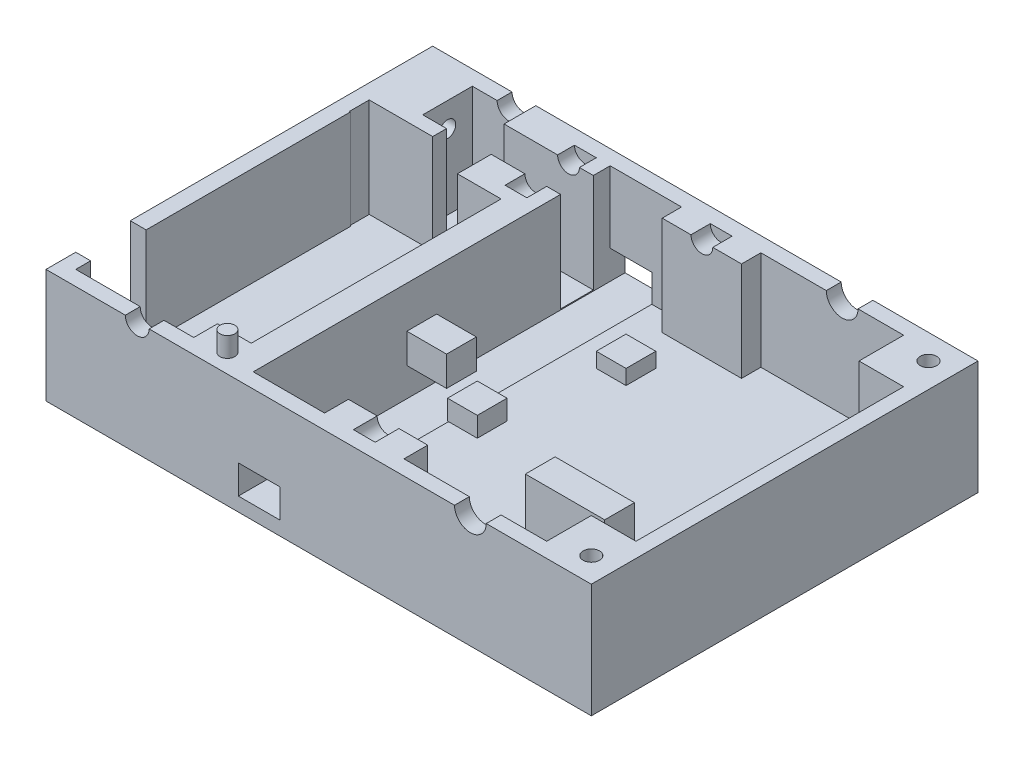
SolidWorks part; units mm, degrees
ref_plane "前视基准面" through (0, 0, 0) normal (0, 0, 1) x (1, 0, 0)
ref_plane "上视基准面" through (0, 0, 0) normal (0, 1, 0) x (1, 0, 0)
ref_plane "右视基准面" through (0, 0, 0) normal (1, 0, 0) x (0, 0, -1)
other "Configuration Table"
sketch "草图1" plane through (0, 0, 0) normal (0, 1, 0) x (1, 0, 0)
  line L1 (-27.5, 19.5) -> (27.5, 19.5)
  line L2 (-27.5, 19.5) -> (-27.5, -19.5)
  line L3 (-27.5, -19.5) -> (27.5, -19.5)
  line L4 (27.5, 19.5) -> (27.5, -19.5)
  line L5 (-27.5, 19.5) -> (27.5, -19.5) construction
  line L6 (-27.5, -19.5) -> (27.5, 19.5) construction
  point P0 (0, 0)
  dimension "D1" = 55
  dimension "D2" = 39
extrude "凸台-拉伸1" add sketch "草图1" along normal blind 11.5
shell "抽壳1" thickness 1.5 removed face at (0, 11.5, 0)
sketch "草图2" plane through (0, 0, -19.5) normal (0, 0, -1) x (-1, 0, 0)
  line L0 (7.9, 1.6) -> (4.1, 1.6) construction
  line L1 (3.9, 4.3) -> (8.1, 4.3)
  line L2 (3.9, 4.3) -> (3.9, 1.4)
  line L3 (3.9, 1.4) -> (8.1, 1.4)
  line L4 (8.1, 4.3) -> (8.1, 1.4)
  line L5 (7.9, 1.6) -> (7.9, 4.1) construction
  line L6 (7.9, 4.1) -> (4.1, 4.1) construction
  line L7 (4.1, 1.6) -> (4.1, 4.1) construction
  circle A0 centre (-15.3, 11.5) radius 1.6
  circle A1 centre (18.3, 11.5) radius 1.2
  circle A2 centre (-15.3, 11.5) radius 1.5 construction
  circle A3 centre (18.3, 11.5) radius 1 construction
  dimension "D1" = 0.1
  dimension "D2" = 0.2
  dimension "D3" = 0.2
  dimension "D4" = 0.2
  dimension "D5" = 0.2
  dimension "D6" = 0.2
extrude "切除-拉伸1" cut sketch "草图2" against normal through all
sketch "草图3" plane through (0, 1.5, 0) normal (0, 1, 0) x (1, 0, 0)
  line L0 (-25.8, -15.5) -> (-10.8, -15.5) construction
  line L5 (-10.7, 9.6) -> (-10.7, -15.6)
  line L6 (-15.1, 13) -> (-8.1, 13)
  line L7 (-15.1, 13) -> (-15.1, 9.6)
  line L8 (-15.1, 9.6) -> (-10.7, 9.6)
  line L10 (-17.1, -18) -> (13.7, -18) construction
  line L11 (-10.7, -18) -> (-8.1, -18)
  line L13 (-14.3, -17.8) -> (-14.3, -15.5) construction
  line L14 (-28.8, -11) -> (-25.8, -11) construction
  line L15 (-26, 9.6) -> (-25.9, 9.6)
  line L16 (-15.3, 9.5) -> (-15.3, 11.5) construction
  line L17 (-10.8, 9.5) -> (-10.8, -15.5) construction
  line L18 (-8.1, 18) -> (-8.1, -18) construction
  line L19 (13.7, 18) -> (-17.1, 18) construction
  line L20 (-17.1, 18) -> (-8.1, 18)
  line L21 (-17.1, 18) -> (-17.1, 16.3)
  line L22 (-17.1, 16.3) -> (-8.1, 16.3)
  line L23 (-8.1, 18) -> (-8.1, 16.3)
  line L24 (-17.1, 18) -> (-17.1, 19.5) construction
  line L25 (-8.1, 13) -> (-8.1, -18)
  line L26 (4.6159, 15.85) -> (4.2435, 15.85) construction
  line L27 (-0.9, 18) -> (7.1, 18)
  line L28 (-0.9, 18) -> (-0.9, 16.05)
  line L29 (-0.9, 16.05) -> (7.1, 16.05)
  line L30 (7.1, 18) -> (7.1, 16.05)
  line L31 (4.1, -17.4593) -> (4.1, 18.8407) construction
  line L32 (-17.1, -18) -> (13.7, -18) construction
  line L33 (-0.9, -15.6) -> (7.1, -15.6)
  line L34 (-0.9, -15.6) -> (-0.9, -18)
  line L35 (-0.9, -18) -> (7.1, -18)
  line L36 (7.1, -15.6) -> (7.1, -18)
  line L37 (-26, 9.6) -> (-26, -11)
  line L38 (26, 18) -> (16.9, 18) construction
  line L39 (21.5, 18) -> (26, 18)
  line L40 (21.5, 18) -> (21.5, 13.5)
  line L41 (21.5, 13.5) -> (26, 13.5)
  line L42 (26, 18) -> (26, 13.5)
  line L43 (26, -18) -> (26, 18) construction
  line L44 (-26, 18) -> (-26, -18) construction
  line L45 (21.5, -13.5) -> (26, -13.5)
  line L46 (21.5, -13.5) -> (21.5, -18)
  line L47 (21.5, -18) -> (26, -18)
  line L48 (26, -13.5) -> (26, -18)
  line L49 (-26, 18) -> (-22, 18)
  line L50 (-26, 18) -> (-26, 13)
  line L52 (-22, 18) -> (-22, 13)
  line L53 (-26, 11.6) -> (-19.6, 11.6)
  line L54 (-26, 11.6) -> (-26, 13)
  line L55 (-22, 13) -> (-19.6, 13)
  line L56 (-19.6, 11.6) -> (-19.6, 13)
  line L57 (-15.3, 11.5) -> (-21.3, 11.5) construction
  line L58 (-19.3, 19) -> (-19.3, 11.5) construction
  line L59 (-10.8, 9.5) -> (-25.8, 9.5) construction
  line L60 (-19.5, 18) -> (-26, 18) construction
  line L61 (-26, -11) -> (-25.9, -11)
  line L62 (-14.1, -15.6) -> (-10.7, -15.6)
  line L63 (-14.1, -15.6) -> (-14.1, -18)
  line L64 (-14.1, -18) -> (-10.7, -18)
  line L65 (-25.9, 9.6) -> (-25.9, -11)
  dimension "D2" = 4
  dimension "D3" = 0.1
  dimension "D4" = 0.2
  dimension "D5" = 1.7
  dimension "D6" = 0.1
  dimension "D7" = 8
  dimension "D8" = 0.2
  dimension "D9" = 3
  dimension "D10" = 8
  dimension "D11" = 3
  dimension "D12" = 2.4
  dimension "D13" = 4.5
  dimension "D14" = 4.5
  dimension "D15" = 4.5
  dimension "D16" = 4.5
  dimension "D17" = 0.3
  dimension "D18" = 0.1
  dimension "D19" = 5
  dimension "D20" = 0.1
  dimension "D21" = 0.2
  dimension "D22" = 0.1
extrude "凸台-拉伸2" add sketch "草图3" along normal up to surface (10 mm away) up to face at (-23.125, 11.5, 0)
sketch "草图4" plane through (0, 0, 19.5) normal (0, 0, 1) x (1, 0, 0)
  circle A0 centre (3.1, 11.5) radius 1.1
  circle A1 centre (3.1, 11.5) radius 1 construction
  dimension "D1" = 0.1
extrude "切除-拉伸2" cut sketch "草图4" against normal offset from surface (36 mm away) 1.5 from offset 1.5 up to face at (-6, 2.85, -19.5) offset against normal yes
sketch "草图5" plane through (0, 0, -19.5) normal (0, 0, -1) x (-1, 0, 0)
  circle A0 centre (10.6, 11.5) radius 1.1
  circle A1 centre (10.6, 11.5) radius 1 construction
  dimension "D1" = 0.1
extrude "切除-拉伸3" cut sketch "草图5" against normal blind 7 from offset 1.5 offset against normal yes
sketch "草图6" plane through (0, 1.5, 0) normal (0, 1, 0) x (1, 0, 0)
  line L0 (-0.9, 18) -> (-8.1, 18) construction
  line L1 (-1.1, 12.6) -> (1.9, 12.6)
  line L2 (-1.1, 12.6) -> (-1.1, 9.6)
  line L3 (-1.1, 9.6) -> (1.9, 9.6)
  line L4 (1.9, 12.6) -> (1.9, 9.6)
  line L6 (-8.1, -18) -> (-8.1, 13) construction
  line L8 (-32, 4) -> (-27.5, 4)
  line L9 (-32, 4) -> (-32, -4)
  line L10 (-32, -4) -> (-27.5, -4)
  line L11 (-27.5, 4) -> (-27.5, -4)
  line L14 (-27.5, 0) -> (-45.462, 0) construction
  line L15 (-27.5, 19.5) -> (-27.5, -19.5) construction
  dimension "D1" = 8.4
  dimension "D2" = 3
  dimension "D3" = 3
  dimension "D4" = 7
  dimension "D5" = 4.5
  dimension "D6" = 8
extrude "变速卡位凸台-拉伸3" add sketch "草图6" along normal blind 1.5 and the other way blind 1.5
sketch "草图7" plane through (0, 0, 0) normal (0, -1, 0) x (1, 0, 0)
  line L0 (-32, -4) -> (-32, 4) construction
  line L1 (27.5, 0) -> (56.3628, 0) construction
  line L2 (27.5, 19.5) -> (27.5, -19.5) construction
  line L3 (21.5, 13.5) -> (21.5, 18) construction
  line L4 (26, 13.5) -> (21.5, 13.5) construction
  circle A0 centre (-29.8, 0) radius 1
  circle A1 centre (25, 17) radius 0.825
  circle A2 centre (25, -17) radius 0.825
  dimension "D1" = 2
  dimension "D2" = 2.2
  dimension "D3" = 1.65
  dimension "D4" = 3.5
  dimension "D5" = 3.5
extrude "盖子固定切除-拉伸4" cut sketch "草图7" against normal through all
sketch "草图8" plane through (0, 1.5, 0) normal (0, 1, 0) x (1, 0, 0)
  line L0 (27.5, 0) -> (45.6897, 0) construction
  line L1 (27.5, -19.5) -> (27.5, 19.5) construction
  line L2 (26, -13.5) -> (26, 13.5) construction
  line L3 (26, -13.5) -> (21.5, -13.5) construction
  circle A0 centre (23, 7.6) radius 1
  circle A1 centre (23, -10.5) radius 1
  dimension "D1" = 2
  dimension "D2" = 3
  dimension "D3" = 3
  dimension "D4" = 2
  dimension "D5" = 3
  dimension "D6" = 3
extrude "底部螺丝孔切除-拉伸5" cut sketch "草图8" against normal through all
sketch "草图9" plane through (-27.5, 0, 0) normal (-1, 0, 0) x (0, 0, 1)
  line L0 (-19.5, 11.5) -> (19.5, 11.5) construction
  line L1 (-18, 11.5) -> (-18, 1.5) construction
  circle A0 centre (-15.502, 9) radius 0.825
  dimension "D1" = 1.65
  dimension "D2" = 2.5
  dimension "D3" = 2.498
extrude "前螺丝孔切除-拉伸6" cut sketch "草图9" against normal up to next
sketch "草图10" plane through (0, 1.5, 0) normal (0, 1, 0) x (1, 0, 0)
  line L0 (16.8, -23.2416) -> (16.8, 22.7584) construction
  line L1 (11.55, -7.2) -> (19.55, -7.2)
  line L2 (11.55, -7.2) -> (11.55, -10.2)
  line L3 (11.55, -10.2) -> (19.55, -10.2)
  line L4 (19.55, -7.2) -> (19.55, -10.2)
  line L5 (16.0993, -7.1) -> (16.9803, -7.1) construction
  dimension "D1" = 8
  dimension "D2" = 2.75
  dimension "D3" = 0.1
  dimension "D4" = 3
extrude "3mm轴卡位凸台-拉伸4" add sketch "草图10" along normal blind 7
sketch "草图11" plane through (-27.5, 0, 0) normal (-1, 0, 0) x (0, 0, 1)
  line L1 (16.5, 3.5) -> (11, 3.5)
  line L2 (16.5, 3.5) -> (16.5, 11.5)
  line L3 (16.5, 11.5) -> (11, 11.5)
  line L4 (11, 3.5) -> (11, 11.5)
  line L5 (-19.5, 11.5) -> (19.5, 11.5) construction
  line L6 (11, 7.5) -> (11, 3.5) construction
extrude "切除-拉伸4" cut sketch "草图11" against normal up to next
sketch "草图12" plane through (0, 11.5, 0) normal (0, 1, 0) x (1, 0, 0)
  line L0 (-8.1, -18) -> (-8.1, 13) construction
  line L1 (-10.7, -15.6) -> (-14.1, -15.6) construction
  circle A0 centre (-11.1, -17.6) radius 0.75
  dimension "D1" = 1.5
  dimension "D2" = 3
  dimension "D3" = 2
extrude "凸台-拉伸5" add sketch "草图12" along normal blind 2
sketch "草图13" plane through (-8.1, 0, 0) normal (1, 0, 0) x (0, 0, -1)
  line L0 (-19.5, 4.3) -> (-18, 4.3) construction
  line L1 (-2.5, 4.3) -> (0.5, 4.3)
  line L2 (-2.5, 4.3) -> (-2.5, 7.3)
  line L3 (-2.5, 7.3) -> (0.5, 7.3)
  line L4 (0.5, 4.3) -> (0.5, 7.3)
  line L5 (-19.5, 11.5) -> (-19.5, 0) construction
  dimension "D1" = 3
  dimension "D2" = 3
  dimension "D3" = 17
extrude "凸台-拉伸6" add sketch "草图13" along normal blind 4
sketch "草图14" plane through (0, 1.5, 0) normal (0, 1, 0) x (1, 0, 0)
  line L1 (-4, 0.5) -> (-1, 0.5)
  line L2 (-4, 0.5) -> (-4, -2.5)
  line L3 (-4, -2.5) -> (-1, -2.5)
  line L4 (-1, 0.5) -> (-1, -2.5)
  line L5 (-4.1, -2.5) -> (-8.1, -2.5) construction
  line L6 (-4.1, 0.5) -> (-8.1, 0.5) construction
  line L7 (-8.1, -18) -> (-8.1, 13) construction
  dimension "D1" = 3
  dimension "D2" = 4.1
extrude "凸台-拉伸7" add sketch "草图14" along normal blind 2
